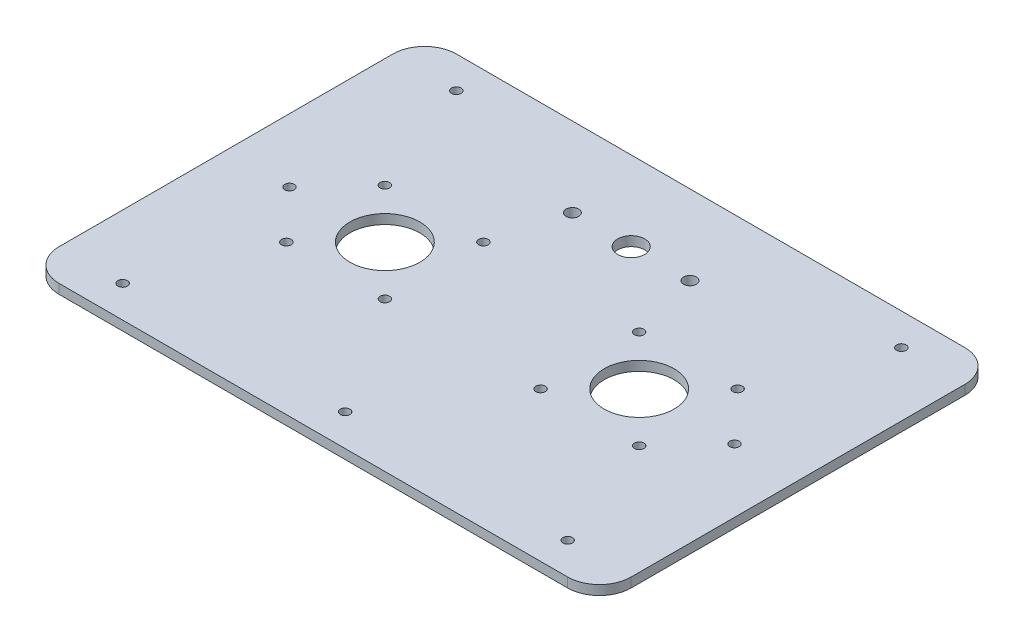
SolidWorks part; units mm, degrees
material "1060 合金"
ref_plane "前视基准面" through (0, 0, 0) normal (0, 0, 1) x (1, 0, 0)
ref_plane "上视基准面" through (0, 0, 0) normal (0, 1, 0) x (1, 0, 0)
ref_plane "右视基准面" through (0, 0, 0) normal (1, 0, 0) x (0, 0, -1)
sketch "草图1" plane through (0, 0, 0) normal (0, 1, 0) x (1, 0, 0)
  line L1 (-80, 62.5) -> (80, 62.5)
  line L2 (-90, 52.5) -> (-90, -52.5)
  line L3 (-80, -62.5) -> (80, -62.5)
  line L4 (90, 52.5) -> (90, -52.5)
  line L5 (-90, 62.5) -> (90, -62.5) construction
  line L6 (-90, -62.5) -> (90, 62.5) construction
  arc A0 (-90, -52.5) -> (-80, -62.5) centre (-80, -52.5) ccw
  arc A1 (80, -62.5) -> (90, -52.5) centre (80, -52.5) ccw
  arc A2 (90, 52.5) -> (80, 62.5) centre (80, 52.5) ccw
  arc A3 (-80, 62.5) -> (-90, 52.5) centre (-80, 52.5) ccw
  circle A4 centre (-70, 52.5) radius 1.5
  circle A5 centre (-70, 0) radius 1.5
  circle A7 centre (-70, -52.5) radius 1.5
  circle A8 centre (0, -52.5) radius 1.5
  circle A9 centre (70, -52.5) radius 1.5
  circle A10 centre (70, 0) radius 1.5
  circle A11 centre (70, 52.5) radius 1.5
  circle A12 centre (0, 37.5) radius 4.25
  circle A13 centre (-18.5, 37.5) radius 2
  circle A14 centre (18.5, 37.5) radius 2
  circle A15 centre (40, 0) radius 11
  circle A16 centre (-40, 0) radius 11
  circle A17 centre (55.5, 15.5) radius 1.5
  circle A18 centre (55.5, -15.5) radius 1.5
  circle A19 centre (24.5, -15.5) radius 1.5
  circle A20 centre (24.5, 15.5) radius 1.5
  circle A21 centre (-24.5, 15.5) radius 1.5
  circle A22 centre (-24.5, -15.5) radius 1.5
  circle A23 centre (-55.5, -15.5) radius 1.5
  circle A24 centre (-55.5, 15.5) radius 1.5
  point P0 (0, 0)
  point P53 (40, 0)
  point P62 (-40, 0)
  dimension "D3" = 10
  dimension "D4" = 3
  dimension "D5" = 3
  dimension "D6" = 3
  dimension "D7" = 3
  dimension "D8" = 3
  dimension "D9" = 3
  dimension "D10" = 3
  dimension "D11" = 20
  dimension "D12" = 20
  dimension "D13" = 20
  dimension "D14" = 20
  dimension "D15" = 20
  dimension "D16" = 20
  dimension "D17" = 10
  dimension "D18" = 10
  dimension "D19" = 10
  dimension "D20" = 10
  dimension "D21" = 10
  dimension "D22" = 62.5
  dimension "D23" = 62.5
  dimension "D24" = 8.5
  dimension "D25" = 4
  dimension "D26" = 4
  dimension "D28" = 25
  dimension "D29" = 25
  dimension "D30" = 18.5
  dimension "D31" = 18.5
  dimension "D32" = 90
  dimension "D33" = 22
  dimension "D34" = 22
  dimension "D35" = 40
  dimension "D36" = 40
  dimension "D37" = 62.5
  dimension "D38" = 62.5
  dimension "D39" = 3
  dimension "D41" = 15.5
  dimension "D42" = 15.5
  dimension "D43" = 15.5
  dimension "D44" = 15.5
  dimension "D45" = 15.5
  dimension "D46" = 15.5
  dimension "D47" = 15.5
  dimension "D48" = 3
  dimension "D49" = 3
  dimension "D50" = 3
  dimension "D51" = 3
  dimension "D52" = 15.5
  dimension "D53" = 15.5
  dimension "D54" = 15.5
  dimension "D55" = 15.5
  dimension "D56" = 15.5
  dimension "D57" = 15.5
  dimension "D58" = 15.5
  dimension "D59" = 15.5
  dimension "D60" = 3
  dimension "D61" = 3
  dimension "D62" = 3
  dimension "D63" = 90
  dimension "D1" = 125
  dimension "D2" = 180
  dimension "D27" = 25
  dimension "D40" = 15.5
base flange "基体-法兰1" sketch "草图1" thickness 3 reverse thickness direction no parameters "D1"=0.7366
sketch "折弯-线1" plane through (0, 0, 0) normal (0, 1, 0) x (1, 0, 0)
sketch "边界框1" plane through (0, 0, 0) normal (0, 1, 0) x (1, 0, 0)
sheet metal parameters "钣金7" thickness 3 parameters "D1"=0.7366
flat pattern "平板型式7" [suppressed]
sketch "折弯-线2" plane through (0, 0, 0) normal (0, 1, 0) x (1, 0, 0)
sketch "边界框2" [suppressed] plane through (0, 0, 0) normal (0, 1, 0) x (1, 0, 0)
